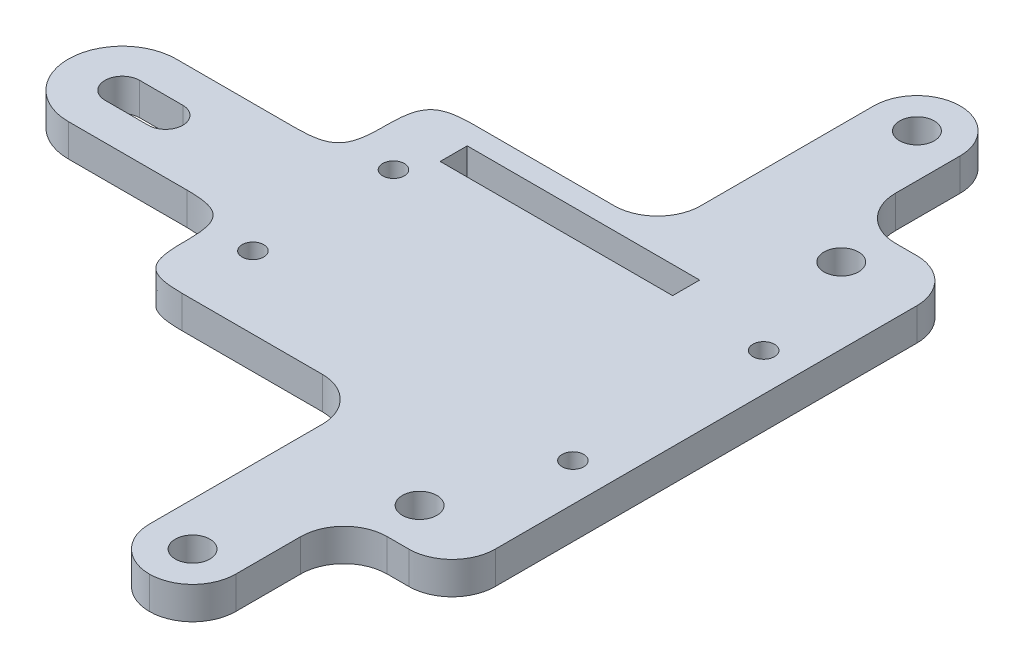
SolidWorks part; units mm, degrees
material "Caucho"
ref_plane "Alzado" through (0, 0, 0) normal (0, 0, 1) x (1, 0, 0)
ref_plane "Planta" through (0, 0, 0) normal (0, 1, 0) x (1, 0, 0)
ref_plane "Vista lateral" through (0, 0, 0) normal (1, 0, 0) x (0, 0, -1)
sketch "Croquis1" plane through (0, 0, 0) normal (0, 1, 0) x (1, 0, 0)
  line L1 (-40.5, -23.5) -> (40.5, -23.5)
  line L2 (-40.5, -23.5) -> (-40.5, 23.5)
  line L3 (-40.5, 23.5) -> (40.5, 23.5)
  line L4 (40.5, -23.5) -> (40.5, 23.5)
  line L5 (-40.5, -23.5) -> (40.5, 23.5) construction
  line L6 (-40.5, 23.5) -> (40.5, -23.5) construction
  point P0 (0, 0)
  dimension "D1" = 81
  dimension "D2" = 47
extrude "Saliente-Extruir1" add sketch "Croquis1" along normal blind 3
sketch "Croquis3" plane through (0, 3, 0) normal (0, 1, 0) x (1, 0, 0)
  line L1 (-32.5, 23.5) -> (23.5, 23.5)
  line L2 (-32.5, 23.5) -> (-32.5, 5)
  line L4 (23.5, 23.5) -> (23.5, 13.5)
  line L6 (-32.5, -5) -> (-32.5, -23.5)
  line L7 (-32.5, -23.5) -> (23.5, -23.5)
  line L8 (23.5, -13.5) -> (23.5, -23.5)
  line L9 (40.5, 23.5) -> (-40.5, 23.5) construction
  line L18 (-32.5, 5) -> (-4.5, 5)
  line L19 (-40.5, 23.5) -> (-40.5, -23.5) construction
  line L20 (-40.5, -23.5) -> (40.5, -23.5) construction
  line L21 (-4.5, 5) -> (-4.5, 13.5)
  line L22 (40.5, -23.5) -> (40.5, 23.5) construction
  line L23 (-4.5, 13.5) -> (23.5, 13.5)
  line L25 (-32.5, -5) -> (-4.5, -5)
  line L26 (-4.5, -5) -> (-4.5, -13.5)
  line L27 (-4.5, -13.5) -> (23.5, -13.5)
  point P12 (0, 0)
  dimension "D1" = 10
  dimension "D2" = 17
  dimension "D3" = 28
  dimension "D4" = 10
  dimension "D8" = 8
extrude "Cortar-Extruir2" cut sketch "Croquis3" against normal through all
sketch "Croquis2" plane through (0, 3, 0) normal (0, 1, 0) x (1, 0, 0)
  line L7 (-40.5, 19.5) -> (-32.5, 19.5) construction
  line L13 (36.5, -19.5) -> (-36.5, -19.5) construction
  line L14 (36.5, -19.5) -> (36.5, 19.5) construction
  line L15 (36.5, 19.5) -> (-36.5, 19.5) construction
  line L16 (-36.5, -19.5) -> (-36.5, 19.5) construction
  line L17 (36.5, -19.5) -> (-36.5, 19.5) construction
  line L22 (-36.5, -11.5) -> (-36.5, 11.5) construction
  line L23 (36.5, 19.5) -> (-36.5, -19.5) construction
  line L24 (-40.5, 23.5) -> (-40.5, -23.5) construction
  line L25 (-32.5, 23.5) -> (-32.5, 5) construction
  line L26 (27.5, 19.5) -> (27.5, -19.5) construction
  circle A16 centre (-36.5, 19.5) radius 1.6
  circle A18 centre (-36.5, -19.5) radius 1.6
  circle A20 centre (27.5, 19.5) radius 1.6
  circle A21 centre (27.5, -19.5) radius 1.6
  circle A22 centre (-36.5, 11.5) radius 1.6
  circle A23 centre (-36.5, -11.5) radius 1.6
  point P0 (0, 0)
  point P26 (-36.5, 11.5)
  point P27 (-36.5, 0)
  dimension "D1" = 39
  dimension "D2" = 3.2
  dimension "D4" = 23
  dimension "D3" = 9
extrude "Cortar-Extruir1" cut sketch "Croquis2" against normal through all
sketch "Croquis5" plane through (0, 3, 0) normal (0, 1, 0) x (1, 0, 0)
  line L6 (23.5, 13.5) -> (23.5, 23.5) construction
  line L7 (34.5, 31.3071) -> (50.5, 31.3071)
  line L13 (-0.6, 0) -> (31, 0) construction
  line L14 (31, -8.82) -> (31, 8.82) construction
  line L15 (-0.6, 6.18) -> (-0.6, 0) construction
  line L16 (-0.6, 0) -> (-0.6, -6.82) construction
  line L18 (0.9, 11.5) -> (22.4, 11.5)
  line L19 (0.9, 11.5) -> (0.9, 9)
  line L20 (0.9, 9) -> (22.4, 9)
  line L21 (22.4, 11.5) -> (22.4, 9)
  line L22 (34.5, 31.3071) -> (34.5, -27.9356)
  line L25 (34.5, -27.9356) -> (50.5, -27.9356)
  line L26 (50.5, 31.3071) -> (50.5, -27.9356)
  circle A12 centre (-0.6, 6.18) radius 1
  circle A13 centre (31, 8.82) radius 1
  circle A14 centre (31, -8.82) radius 1
  circle A15 centre (-0.6, -6.82) radius 1
  point P0 (0, 0)
  point P32 (31, 0)
  dimension "D2" = 11
  dimension "D5" = 2
  dimension "D3" = 16
  dimension "D7" = 17.64
  dimension "D8" = 6.82
  dimension "D9" = 6.18
  dimension "D10" = 31.6
  dimension "D11" = 31
  dimension "D12" = 2.5
  dimension "D13" = 21.5
  dimension "D14" = 9
  dimension "D15" = 1.5
extrude "Cortar-Extruir4" cut sketch "Croquis5" against normal blind 10
sketch "Croquis6" plane through (0, 3, 0) normal (0, 1, 0) x (1, 0, 0)
  line L0 (-19.5, 0) -> (-15.5, 0) construction
  line L1 (-19.5, 1.6) -> (-15.5, 1.6)
  line L2 (-19.5, -1.6) -> (-15.5, -1.6)
  arc A0 (-19.5, 1.6) -> (-19.5, -1.6) centre (-19.5, 0) ccw
  arc A1 (-15.5, -1.6) -> (-15.5, 1.6) centre (-15.5, 0) ccw
  circle A2 centre (-36.5, 11.5) radius 1.6 construction
  point P3 (-17.5, 0)
  dimension "D2" = 1.6
  dimension "D1" = 4
  dimension "D3" = 19
extrude "Cortar-Extruir5" cut sketch "Croquis6" against normal blind 10
sketch "Croquis7" plane through (0, 3, 0) normal (0, 1, 0) x (1, 0, 0)
  line L1 (-24.5, 28.8052) -> (-52.393, 28.8052)
  line L2 (-24.5, 28.8052) -> (-24.5, -29.9801)
  line L3 (-24.5, -29.9801) -> (-52.393, -29.9801)
  line L4 (-52.393, 28.8052) -> (-52.393, -29.9801)
  arc A0 (-19.5, 1.6) -> (-19.5, -1.6) centre (-19.5, 0) ccw construction
  dimension "D1" = 5
extrude "Cortar-Extruir6" cut sketch "Croquis7" against normal blind 10
sketch "Croquis8" plane through (0, 3, 0) normal (0, 1, 0) x (1, 0, 0)
  line L0 (23.5, -13.5) -> (-4.5, -13.5) construction
  line L2 (16.5, -13.5) -> (16.5, -37.5)
  line L3 (16.5, -37.5) -> (24.5, -37.5)
  line L4 (24.5, -13.5) -> (24.5, -37.5)
  line L5 (16.5, -33.5) -> (24.5, -33.5) construction
  line L6 (16.5, -13.5) -> (24.5, -13.5)
  circle A1 centre (20.5, -33.5) radius 1.6
  circle A5 centre (27.5, -19.5) radius 1.6 construction
  point P13 (20.5, -33.5)
  dimension "D4" = 3.2
  dimension "D3" = 7
  dimension "D1" = 8
  dimension "D2" = 24
  dimension "D5" = 4
extrude "Saliente-Extruir2" add sketch "Croquis8" against normal through all
mirror "Simetría1" about plane through (0, 0, 0) normal (0, 0, 1) of "Saliente-Extruir2"
fillet "Redondeo1" radius 4 10 edges at (34.5, 1.5, 23.5) (34.5, 1.5, -23.5) (16.5, 1.5, 37.5) (24.5, 1.5, 37.5) (16.5, 1.5, 13.5) (24.5, 1.5, 23.5) (24.5, 1.5, -37.5) (16.5, 1.5, -37.5) (16.5, 1.5, -13.5) (24.5, 1.5, -23.5)
fillet "Redondeo4" radius 5 2 edges at (-24.5, 1.5, -5) (-24.5, 1.5, 5)
fillet "Redondeo3" radius 4 4 edges at (-4.5, 1.5, 13.5) (-4.5, 1.5, 5) (-4.5, 1.5, -13.5) (-4.5, 1.5, -5) conic rho 0.6
